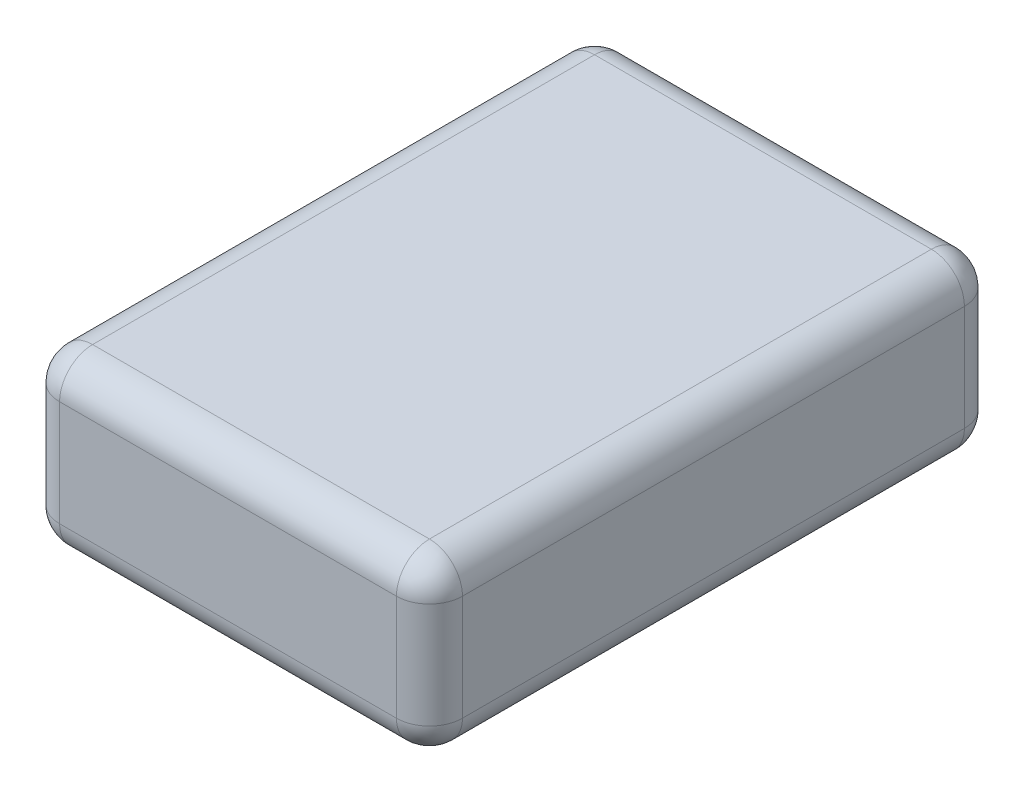
SolidWorks part; units mm, degrees
ref_plane "Front Plane" through (0, 0, 0) normal (0, 0, 1) x (1, 0, 0)
ref_plane "Top Plane" through (0, 0, 0) normal (0, 1, 0) x (1, 0, 0)
ref_plane "Right Plane" through (0, 0, 0) normal (1, 0, 0) x (0, 0, -1)
sketch "Sketch1" plane through (0, 0, 0) normal (0, 1, 0) x (1, 0, 0)
  line L1 (-30.5, -43) -> (30.5, -43)
  line L2 (-30.5, -43) -> (-30.5, 43)
  line L3 (-30.5, 43) -> (30.5, 43)
  line L4 (30.5, -43) -> (30.5, 43)
  line L5 (-30.5, -43) -> (30.5, 43) construction
  line L6 (-30.5, 43) -> (30.5, -43) construction
  point P0 (0, 0)
  dimension "D1" = 86
  dimension "D2" = 61
extrude "Boss-Extrude1" add sketch "Sketch1" along normal blind 26
fillet "Fillet1" radius 5 12 edges at (0, 0, -43) (0, 0, 43) (0, 26, 43) (0, 26, -43) (30.5, 13, 43) (30.5, 26, 0) (30.5, 13, -43) (30.5, 0, 0) (-30.5, 13, -43) (-30.5, 26, 0) (-30.5, 13, 43) (-30.5, 0, 0)
sketch "Sketch2" plane through (0, 0, -43) normal (0, 0, -1) x (-1, 0, 0)
  line L0 (-25.5, 21) -> (-25.5, 5) construction
  line L1 (-5, 18) -> (5, 18)
  line L2 (-5, 18) -> (-5, 8)
  line L3 (-5, 8) -> (5, 8)
  line L4 (5, 18) -> (5, 8)
  line L5 (-25.5, 13) -> (-5, 13) construction
  point P5 (0, 8)
  dimension "D1" = 10
  dimension "D2" = 10
extrude "Cut-Extrude1" cut sketch "Sketch2" against normal blind 10
